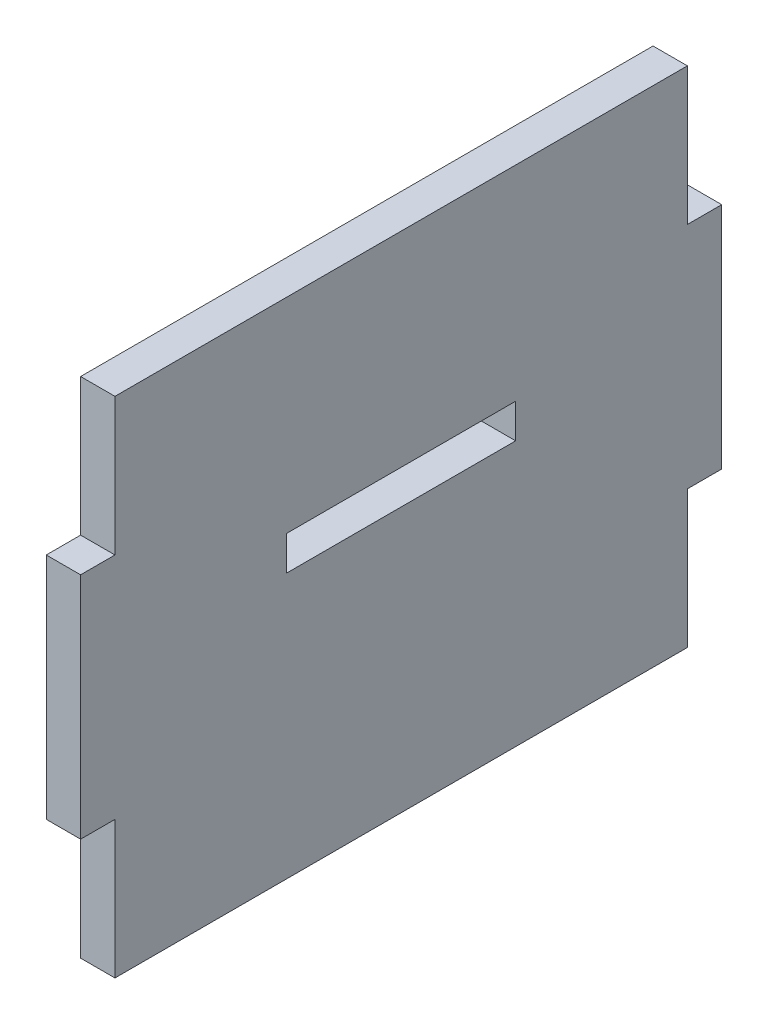
SolidWorks part; units mm, degrees
ref_plane "Front Plane" through (0, 0, 0) normal (0, 0, 1) x (1, 0, 0)
ref_plane "Top Plane" through (0, 0, 0) normal (0, 1, 0) x (1, 0, 0)
ref_plane "Right Plane" through (0, 0, 0) normal (1, 0, 0) x (0, 0, -1)
sketch "Sketch1" plane through (0, 0, 0) normal (1, 0, 0) x (0, 0, -1)
  line L0 (0, 44) -> (0, 32) construction
  line L1 (0, 0) -> (50, 0)
  line L2 (0, 0) -> (0, 12)
  line L3 (0, 44) -> (50, 44)
  line L4 (50, 0) -> (50, 12)
  line L5 (25, 44) -> (25, 0) construction
  line L6 (0, 12) -> (0, 0) construction
  line L7 (-3, 12) -> (0, 12)
  line L8 (-3, 12) -> (-3, 32)
  line L9 (-3, 32) -> (0, 32)
  line L11 (-3, 22) -> (25, 22) construction
  line L12 (53, 12) -> (50, 12)
  line L13 (0, 32) -> (0, 44)
  line L14 (53, 12) -> (53, 32)
  line L15 (53, 32) -> (50, 32)
  line L16 (50, 32) -> (50, 44)
  line L17 (25, 44) -> (25, 24.6327) construction
  line L18 (0, 24.6327) -> (50, 24.6327) construction
  line L20 (15, 23.1327) -> (35, 23.1327)
  line L21 (15, 23.1327) -> (15, 26.1327)
  line L22 (15, 26.1327) -> (35, 26.1327)
  line L23 (35, 23.1327) -> (35, 26.1327)
  line L24 (15, 23.1327) -> (35, 26.1327) construction
  line L25 (15, 26.1327) -> (35, 23.1327) construction
  dimension "D1" = 50
  dimension "D2" = 44
  dimension "D3" = 20
  dimension "D4" = 3
  dimension "D5" = 19.3673
  dimension "D6" = 20
  dimension "D7" = 3
extrude "Boss-Extrude1" add sketch "Sketch1" along normal blind 3
